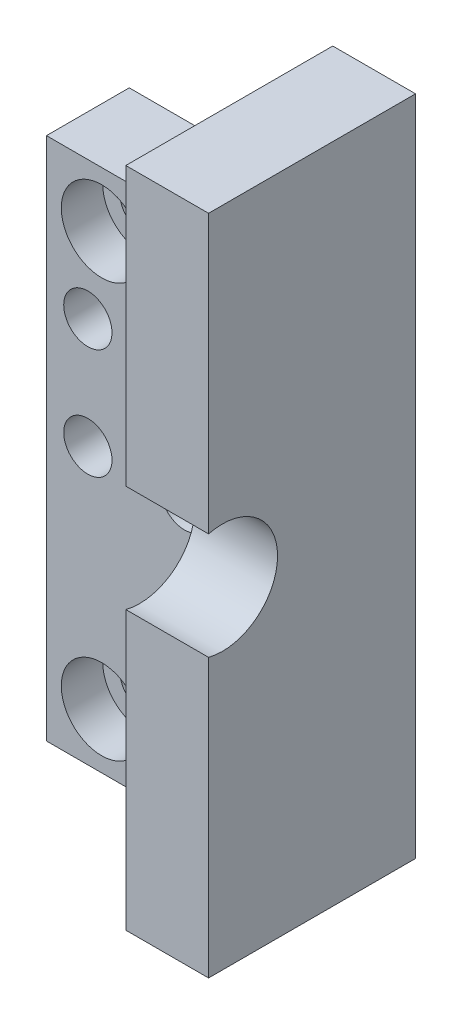
SolidWorks part; units mm, degrees
ref_plane "Front Plane" through (0, 0, 0) normal (0, 0, 1) x (1, 0, 0)
ref_plane "Top Plane" through (0, 0, 0) normal (0, 1, 0) x (1, 0, 0)
ref_plane "Right Plane" through (0, 0, 0) normal (1, 0, 0) x (0, 0, -1)
sketch "Sketch1" plane through (0, 0, 0) normal (0, 0, 1) x (1, 0, 0)
  line L0 (16.75, 48) -> (16.75, 0) construction
  line L1 (0, 0) -> (20.75, 0)
  line L2 (0, 0) -> (0, 48)
  line L3 (0, 48) -> (20.75, 48)
  line L4 (20.75, 0) -> (20.75, 48)
  circle A0 centre (16.75, 34) radius 1.675
  circle A1 centre (16.75, 4) radius 1.675
  dimension "D2" = 3.35
  dimension "D3" = 3.35
  dimension "D1" = 16.75
  dimension "D4" = 30
  dimension "D5" = 14
  dimension "D6" = 4
  dimension "D7" = 4
extrude "Boss-Extrude1" add sketch "Sketch1" along normal blind 6
sketch "Sketch2" plane through (0, 0, 0) normal (-1, 0, 0) x (0, 0, 1)
  line L1 (0, 48) -> (15, 48)
  line L2 (0, 48) -> (0, 0)
  line L3 (0, 0) -> (15, 0)
  line L4 (15, 48) -> (15, 0)
  dimension "D1" = 15
extrude "Boss-Extrude2" add sketch "Sketch2" against normal blind 6
sketch "Sketch3" plane through (0, 0, 0) normal (-1, 0, 0) x (0, 0, 1)
  line L0 (14, 48) -> (14, 0) construction
  line L1 (15, 48) -> (0, 48) construction
  line L2 (15, 0) -> (0, 0) construction
  line L3 (14, 24) -> (14.0919, 24) construction
  line L4 (0, 48) -> (0, 0) construction
  circle A0 centre (14, 24) radius 4
  dimension "D1" = 8
  dimension "D3" = 14
extrude "Cut-Extrude1" cut sketch "Sketch3" against normal blind 6
sketch "Sketch5" plane through (0, 0, 6) normal (0, 0, 1) x (1, 0, 0)
  circle A0 centre (16.75, 34) radius 2.925
  circle A1 centre (16.75, 4) radius 2.925
  dimension "D1" = 5.85
  dimension "D2" = 5.85
extrude "Cut-Extrude2" cut sketch "Sketch5" against normal blind 3
sketch "Sketch6" plane through (0, 0, 6) normal (0, 0, 1) x (1, 0, 0)
  line L0 (20.75, 24) -> (8.4532, 24) construction
  line L1 (20.75, 0) -> (20.75, 48) construction
  circle A0 centre (10.75, 28) radius 1.75
  circle A1 centre (17.75, 28) radius 1.75
  circle A2 centre (10.75, 20) radius 1.75
  circle A3 centre (17.75, 20) radius 1.75
  dimension "D1" = 4
  dimension "D3" = 3.5
  dimension "D4" = 3.5
  dimension "D2" = 4
  dimension "D5" = 7
  dimension "D6" = 3
extrude "Cut-Extrude3" cut sketch "Sketch6" against normal blind 10
sketch "Sketch7" plane through (0, 0, 0) normal (0, 0, -1) x (-1, 0, 0)
  line L1 (-19.5, 28) -> (-16, 28)
  line L2 (-19.5, 28) -> (-19.5, 20)
  line L3 (-19.5, 20) -> (-16, 20)
  line L4 (-16, 28) -> (-16, 20)
  line L5 (-12.5, 20) -> (-9, 20)
  line L6 (-12.5, 20) -> (-12.5, 28)
  line L7 (-12.5, 28) -> (-9, 28)
  line L8 (-9, 20) -> (-9, 28)
  circle A0 centre (-17.75, 28) radius 1.75 construction
  circle A1 centre (-17.75, 20) radius 1.75 construction
  circle A2 centre (-10.75, 20) radius 1.75 construction
  circle A3 centre (-10.75, 28) radius 1.75 construction
extrude "Cut-Extrude4" cut sketch "Sketch7" against normal blind 2.5
sketch "Sketch8" plane through (0, 0, 6) normal (0, 0, 1) x (1, 0, 0)
  line L0 (20.75, 38) -> (6, 38)
  line L1 (20.75, 0) -> (20.75, 48) construction
  line L2 (6, 0) -> (6, 48) construction
  line L3 (6, 38) -> (6, 48)
  line L4 (6, 48) -> (20.75, 48)
  line L5 (20.75, 48) -> (20.75, 38)
  dimension "D1" = 10
extrude "Cut-Extrude5" cut sketch "Sketch8" against normal blind 16
sketch3d "3DSketch3"
  point P0 (20.75, 10.9724, 2.2496)
mirror "Mirror3" about plane through (20.75, 0, 6) normal (-1, 0, 0) of "Boss-Extrude1", "Boss-Extrude2", "Cut-Extrude1", "Cut-Extrude2", "Cut-Extrude3", "Cut-Extrude4", "Cut-Extrude5"
sketch "Sketch9" plane through (0, 0, 0) normal (-1, 0, 0) x (0, 0, 1)
  line L1 (15, 48) -> (0, 48)
  line L2 (15, 48) -> (15, 0)
  line L3 (15, 0) -> (0, 0)
  line L4 (0, 48) -> (0, 0)
extrude "Cut-Extrude6" cut sketch "Sketch9" against normal blind 20.75
